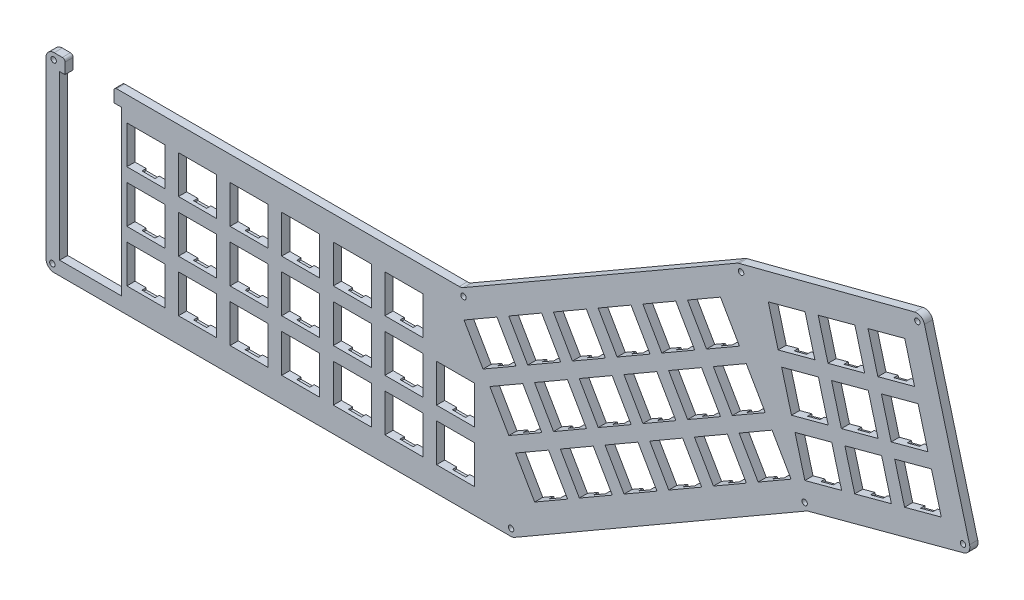
SolidWorks part; units mm, degrees
ref_plane "Plan de face" through (0, 0, 0) normal (0, 0, 1) x (1, 0, 0)
ref_plane "Plan de dessus" through (0, 0, 0) normal (0, 1, 0) x (1, 0, 0)
ref_plane "Plan de droite" through (0, 0, 0) normal (1, 0, 0) x (0, 0, -1)
sketch "Model" plane through (0, 0, 0) normal (0, 0, 1) x (1, 0, 0)
  line L0 (-149.6088, -15.6876) -> (-135.6088, -15.6876) construction
  line L1 (-149.6088, 3.3124) -> (-135.6088, 3.3124) construction
  line L2 (-149.6088, 3.3124) -> (-149.6088, -10.6876) construction
  line L3 (-149.6088, -10.6876) -> (-135.6088, -10.6876) construction
  line L4 (-135.6088, 3.3124) -> (-135.6088, -10.6876) construction
  line L5 (-149.6088, -15.6876) -> (-149.6088, -29.6876) construction
  line L6 (-149.6088, -29.6876) -> (-135.6088, -29.6876) construction
  line L7 (-135.6088, -15.6876) -> (-135.6088, -29.6876) construction
  line L8 (-149.6088, -34.6876) -> (-135.6088, -34.6876) construction
  line L9 (-149.6088, -34.6876) -> (-149.6088, -48.6876) construction
  line L10 (-149.6088, -48.6876) -> (-135.6088, -48.6876) construction
  line L11 (-135.6088, -34.6876) -> (-135.6088, -48.6876) construction
  line L12 (-149.6088, 3.3124) -> (-149.6088, -15.6876) construction
  line L13 (-130.6088, -15.6876) -> (-116.6088, -15.6876) construction
  line L14 (-130.6088, 3.3124) -> (-116.6088, 3.3124) construction
  line L15 (-130.6088, 3.3124) -> (-130.6088, -10.6876) construction
  line L16 (-130.6088, -10.6876) -> (-116.6088, -10.6876) construction
  line L17 (-116.6088, 3.3124) -> (-116.6088, -10.6876) construction
  line L18 (-130.6088, -15.6876) -> (-130.6088, -29.6876) construction
  line L19 (-130.6088, -29.6876) -> (-116.6088, -29.6876) construction
  line L20 (-116.6088, -15.6876) -> (-116.6088, -29.6876) construction
  line L21 (-130.6088, -34.6876) -> (-116.6088, -34.6876) construction
  line L22 (-130.6088, -34.6876) -> (-130.6088, -48.6876) construction
  line L23 (-130.6088, -48.6876) -> (-116.6088, -48.6876) construction
  line L24 (-116.6088, -34.6876) -> (-116.6088, -48.6876) construction
  line L25 (-130.6088, 3.3124) -> (-130.6088, -15.6876) construction
  line L26 (-111.6088, -15.6876) -> (-97.6088, -15.6876) construction
  line L27 (-111.6088, 3.3124) -> (-97.6088, 3.3124) construction
  line L28 (-111.6088, 3.3124) -> (-111.6088, -10.6876) construction
  line L29 (-111.6088, -10.6876) -> (-97.6088, -10.6876) construction
  line L30 (-97.6088, 3.3124) -> (-97.6088, -10.6876) construction
  line L31 (-111.6088, -15.6876) -> (-111.6088, -29.6876) construction
  line L32 (-111.6088, -29.6876) -> (-97.6088, -29.6876) construction
  line L33 (-97.6088, -15.6876) -> (-97.6088, -29.6876) construction
  line L34 (-111.6088, -34.6876) -> (-97.6088, -34.6876) construction
  line L35 (-111.6088, -34.6876) -> (-111.6088, -48.6876) construction
  line L36 (-111.6088, -48.6876) -> (-97.6088, -48.6876) construction
  line L37 (-97.6088, -34.6876) -> (-97.6088, -48.6876) construction
  line L38 (-111.6088, 3.3124) -> (-111.6088, -15.6876) construction
  line L39 (-92.6088, -15.6876) -> (-78.6088, -15.6876) construction
  line L40 (-92.6088, 3.3124) -> (-78.6088, 3.3124) construction
  line L41 (-92.6088, 3.3124) -> (-92.6088, -10.6876) construction
  line L42 (-92.6088, -10.6876) -> (-78.6088, -10.6876) construction
  line L43 (-78.6088, 3.3124) -> (-78.6088, -10.6876) construction
  line L44 (-92.6088, -15.6876) -> (-92.6088, -29.6876) construction
  line L45 (-92.6088, -29.6876) -> (-78.6088, -29.6876) construction
  line L46 (-78.6088, -15.6876) -> (-78.6088, -29.6876) construction
  line L47 (-92.6088, -34.6876) -> (-78.6088, -34.6876) construction
  line L48 (-92.6088, -34.6876) -> (-92.6088, -48.6876) construction
  line L49 (-92.6088, -48.6876) -> (-78.6088, -48.6876) construction
  line L50 (-78.6088, -34.6876) -> (-78.6088, -48.6876) construction
  line L51 (-92.6088, 3.3124) -> (-92.6088, -15.6876) construction
  line L52 (-73.6088, -15.6876) -> (-59.6088, -15.6876) construction
  line L53 (-73.6088, 3.3124) -> (-59.6088, 3.3124) construction
  line L54 (-73.6088, 3.3124) -> (-73.6088, -10.6876) construction
  line L55 (-73.6088, -10.6876) -> (-59.6088, -10.6876) construction
  line L56 (-59.6088, 3.3124) -> (-59.6088, -10.6876) construction
  line L57 (-73.6088, -15.6876) -> (-73.6088, -29.6876) construction
  line L58 (-73.6088, -29.6876) -> (-59.6088, -29.6876) construction
  line L59 (-59.6088, -15.6876) -> (-59.6088, -29.6876) construction
  line L60 (-73.6088, -34.6876) -> (-59.6088, -34.6876) construction
  line L61 (-73.6088, -34.6876) -> (-73.6088, -48.6876) construction
  line L62 (-73.6088, -48.6876) -> (-59.6088, -48.6876) construction
  line L63 (-59.6088, -34.6876) -> (-59.6088, -48.6876) construction
  line L64 (-73.6088, 3.3124) -> (-73.6088, -15.6876) construction
  line L65 (-54.6088, -15.6876) -> (-40.6088, -15.6876) construction
  line L66 (-54.6088, 3.3124) -> (-40.6088, 3.3124) construction
  line L67 (-54.6088, 3.3124) -> (-54.6088, -10.6876) construction
  line L68 (-54.6088, -10.6876) -> (-40.6088, -10.6876) construction
  line L69 (-40.6088, 3.3124) -> (-40.6088, -10.6876) construction
  line L70 (-54.6088, -15.6876) -> (-54.6088, -29.6876) construction
  line L71 (-54.6088, -29.6876) -> (-40.6088, -29.6876) construction
  line L72 (-40.6088, -15.6876) -> (-40.6088, -29.6876) construction
  line L73 (-54.6088, -34.6876) -> (-40.6088, -34.6876) construction
  line L74 (-54.6088, -34.6876) -> (-54.6088, -48.6876) construction
  line L75 (-54.6088, -48.6876) -> (-40.6088, -48.6876) construction
  line L76 (-40.6088, -34.6876) -> (-40.6088, -48.6876) construction
  line L77 (-54.6088, 3.3124) -> (-54.6088, -15.6876) construction
  line L78 (-35.6088, -15.6876) -> (-21.6088, -15.6876) construction
  line L79 (-35.6088, 3.3124) -> (-21.6088, 3.3124) construction
  line L80 (-35.6088, 3.3124) -> (-35.6088, -10.6876) construction
  line L81 (-35.6088, -10.6876) -> (-21.6088, -10.6876) construction
  line L82 (-21.6088, 3.3124) -> (-21.6088, -10.6876) construction
  line L83 (-35.6088, -15.6876) -> (-35.6088, -29.6876) construction
  line L84 (-35.6088, -29.6876) -> (-21.6088, -29.6876) construction
  line L85 (-21.6088, -15.6876) -> (-21.6088, -29.6876) construction
  line L86 (-35.6088, -34.6876) -> (-21.6088, -34.6876) construction
  line L87 (-35.6088, -34.6876) -> (-35.6088, -48.6876) construction
  line L88 (-35.6088, -48.6876) -> (-21.6088, -48.6876) construction
  line L89 (-21.6088, -34.6876) -> (-21.6088, -48.6876) construction
  line L90 (-35.6088, 3.3124) -> (-35.6088, -15.6876) construction
  line L91 (-149.6088, -15.6876) -> (-130.6088, -15.6876) construction
  line L92 (-19.6088, -13.6876) -> (-18.8669, -14.9725) construction
  line L93 (-37.6088, 5.3124) -> (-19.6088, 5.3124) construction
  line L94 (-19.6088, 5.3124) -> (-19.6088, -12.6876) construction
  line L95 (-37.6088, -12.6876) -> (-19.6088, -12.6876) construction
  line L96 (-37.6088, 5.3124) -> (-37.6088, -12.6876) construction
  line L97 (-56.6088, 5.3124) -> (-38.6088, 5.3124) construction
  line L98 (-38.6088, 5.3124) -> (-38.6088, -12.6876) construction
  line L99 (-56.6088, -12.6876) -> (-38.6088, -12.6876) construction
  line L100 (-56.6088, 5.3124) -> (-56.6088, -12.6876) construction
  line L101 (3.8161, 21.7392) -> (12.8161, 6.1508) construction
  line L102 (12.8161, 6.1508) -> (-2.7723, -2.8492) construction
  line L103 (-11.7723, 12.7392) -> (-2.7723, -2.8492) construction
  line L104 (3.8161, 21.7392) -> (-11.7723, 12.7392) construction
  line L105 (-12.6383, 12.2392) -> (-3.6383, -3.3492) construction
  line L106 (-3.6383, -3.3492) -> (-19.2268, -12.3492) construction
  line L107 (-28.2268, 3.2392) -> (-19.2268, -12.3492) construction
  line L108 (-12.6383, 12.2392) -> (-28.2268, 3.2392) construction
  line L109 (88.6341, 26.8303) -> (73.0456, 17.8303) construction
  line L110 (-13.3704, 9.5072) -> (-3.8704, -6.9473) construction
  line L111 (3.0841, 19.0072) -> (12.5841, 2.5527) construction
  line L112 (19.5386, 28.5072) -> (29.0386, 12.0527) construction
  line L113 (35.9931, 38.0072) -> (45.4931, 21.5527) construction
  line L114 (52.4475, 47.5072) -> (61.9475, 31.0527) construction
  line L115 (68.902, 57.0072) -> (78.402, 40.5527) construction
  line L116 (73.0456, 17.8303) -> (82.0456, 2.2418) construction
  line L117 (-6.4947, -30.4018) -> (0.5053, -42.5261) construction
  line L118 (12.6296, -35.5261) -> (0.5053, -42.5261) construction
  line L119 (5.6296, -23.4018) -> (12.6296, -35.5261) construction
  line L120 (5.6296, -23.4018) -> (-6.4947, -30.4018) construction
  line L121 (-15.9947, -13.9473) -> (-8.9947, -26.0717) construction
  line L122 (3.1296, -19.0717) -> (-8.9947, -26.0717) construction
  line L123 (-3.8704, -6.9473) -> (3.1296, -19.0717) construction
  line L124 (-25.4947, 2.5072) -> (-18.4947, -9.6172) construction
  line L125 (-6.3704, -2.6172) -> (-18.4947, -9.6172) construction
  line L126 (-13.3704, 9.5072) -> (-6.3704, -2.6172) construction
  line L127 (-13.3704, 9.5072) -> (-25.4947, 2.5072) construction
  line L128 (-3.8704, -6.9473) -> (-15.9947, -13.9473) construction
  line L129 (9.9597, -20.9018) -> (16.9597, -33.0261) construction
  line L130 (29.0841, -26.0261) -> (16.9597, -33.0261) construction
  line L131 (22.0841, -13.9018) -> (29.0841, -26.0261) construction
  line L132 (22.0841, -13.9018) -> (9.9597, -20.9018) construction
  line L133 (0.4597, -4.4473) -> (7.4597, -16.5717) construction
  line L134 (19.5841, -9.5717) -> (7.4597, -16.5717) construction
  line L135 (12.5841, 2.5527) -> (19.5841, -9.5717) construction
  line L136 (-9.0403, 12.0072) -> (-2.0403, -0.1172) construction
  line L137 (10.0841, 6.8828) -> (-2.0403, -0.1172) construction
  line L138 (3.0841, 19.0072) -> (10.0841, 6.8828) construction
  line L139 (3.0841, 19.0072) -> (-9.0403, 12.0072) construction
  line L140 (12.5841, 2.5527) -> (0.4597, -4.4473) construction
  line L141 (26.4142, -11.4018) -> (33.4142, -23.5261) construction
  line L142 (45.5386, -16.5261) -> (33.4142, -23.5261) construction
  line L143 (38.5386, -4.4018) -> (45.5386, -16.5261) construction
  line L144 (38.5386, -4.4018) -> (26.4142, -11.4018) construction
  line L145 (16.9142, 5.0527) -> (23.9142, -7.0717) construction
  line L146 (36.0386, -0.0717) -> (23.9142, -7.0717) construction
  line L147 (29.0386, 12.0527) -> (36.0386, -0.0717) construction
  line L148 (7.4142, 21.5072) -> (14.4142, 9.3828) construction
  line L149 (26.5386, 16.3828) -> (14.4142, 9.3828) construction
  line L150 (19.5386, 28.5072) -> (26.5386, 16.3828) construction
  line L151 (19.5386, 28.5072) -> (7.4142, 21.5072) construction
  line L152 (29.0386, 12.0527) -> (16.9142, 5.0527) construction
  line L153 (42.8687, -1.9018) -> (49.8687, -14.0261) construction
  line L154 (61.9931, -7.0261) -> (49.8687, -14.0261) construction
  line L155 (54.9931, 5.0982) -> (61.9931, -7.0261) construction
  line L156 (54.9931, 5.0982) -> (42.8687, -1.9018) construction
  line L157 (33.3687, 14.5527) -> (40.3687, 2.4283) construction
  line L158 (52.4931, 9.4283) -> (40.3687, 2.4283) construction
  line L159 (45.4931, 21.5527) -> (52.4931, 9.4283) construction
  line L160 (23.8687, 31.0072) -> (30.8687, 18.8828) construction
  line L161 (42.9931, 25.8828) -> (30.8687, 18.8828) construction
  line L162 (35.9931, 38.0072) -> (42.9931, 25.8828) construction
  line L163 (35.9931, 38.0072) -> (23.8687, 31.0072) construction
  line L164 (45.4931, 21.5527) -> (33.3687, 14.5527) construction
  line L165 (59.3232, 7.5982) -> (66.3232, -4.5261) construction
  line L166 (78.4475, 2.4739) -> (66.3232, -4.5261) construction
  line L167 (71.4475, 14.5982) -> (78.4475, 2.4739) construction
  line L168 (71.4475, 14.5982) -> (59.3232, 7.5982) construction
  line L169 (49.8232, 24.0527) -> (56.8232, 11.9283) construction
  line L170 (68.9475, 18.9283) -> (56.8232, 11.9283) construction
  line L171 (61.9475, 31.0527) -> (68.9475, 18.9283) construction
  line L172 (40.3232, 40.5072) -> (47.3232, 28.3828) construction
  line L173 (59.4475, 35.3828) -> (47.3232, 28.3828) construction
  line L174 (52.4475, 47.5072) -> (59.4475, 35.3828) construction
  line L175 (52.4475, 47.5072) -> (40.3232, 40.5072) construction
  line L176 (61.9475, 31.0527) -> (49.8232, 24.0527) construction
  line L177 (75.7777, 17.0982) -> (82.7777, 4.9739) construction
  line L178 (94.902, 11.9739) -> (82.7777, 4.9739) construction
  line L179 (87.902, 24.0982) -> (94.902, 11.9739) construction
  line L180 (87.902, 24.0982) -> (75.7777, 17.0982) construction
  line L181 (66.2777, 33.5527) -> (73.2777, 21.4283) construction
  line L182 (85.402, 28.4283) -> (73.2777, 21.4283) construction
  line L183 (78.402, 40.5527) -> (85.402, 28.4283) construction
  line L184 (56.7777, 50.0072) -> (63.7777, 37.8828) construction
  line L185 (75.902, 44.8828) -> (63.7777, 37.8828) construction
  line L186 (68.902, 57.0072) -> (75.902, 44.8828) construction
  line L187 (68.902, 57.0072) -> (56.7777, 50.0072) construction
  line L188 (78.402, 40.5527) -> (66.2777, 33.5527) construction
  line L189 (97.6341, 11.2418) -> (82.0456, 2.2418) construction
  line L190 (88.6341, 26.8303) -> (97.6341, 11.2418) construction
  line L191 (102.6968, 0.3259) -> (93.4333, 22.69) construction
  line L192 (93.8992, 29.0112) -> (98.558, 11.6245) construction
  line L193 (98.558, 11.6245) -> (115.9446, 16.2832) construction
  line L194 (111.2859, 33.6699) -> (115.9446, 16.2832) construction
  line L195 (86.5136, 64.3021) -> (91.4311, 45.9495) construction
  line L196 (93.8992, 29.0112) -> (111.2859, 33.6699) construction
  line L197 (91.4311, 45.9495) -> (104.9541, 49.573) construction
  line L198 (86.5136, 64.3021) -> (100.0365, 67.9256) construction
  line L199 (86.5136, 64.3021) -> (90.137, 50.7792) construction
  line L200 (90.137, 50.7792) -> (103.66, 54.4026) construction
  line L201 (100.0365, 67.9256) -> (103.66, 54.4026) construction
  line L202 (91.4311, 45.9495) -> (95.0546, 32.4266) construction
  line L203 (95.0546, 32.4266) -> (108.5776, 36.05) construction
  line L204 (104.9541, 49.573) -> (108.5776, 36.05) construction
  line L205 (96.3487, 27.5969) -> (109.8717, 31.2204) construction
  line L206 (96.3487, 27.5969) -> (99.9722, 14.074) construction
  line L207 (99.9722, 14.074) -> (113.4951, 17.6974) construction
  line L208 (109.8717, 31.2204) -> (113.4951, 17.6974) construction
  line L209 (109.7837, 50.8671) -> (123.3067, 54.4906) construction
  line L210 (104.8662, 69.2197) -> (118.3891, 72.8432) construction
  line L211 (104.8662, 69.2197) -> (108.4896, 55.6967) construction
  line L212 (108.4896, 55.6967) -> (122.0126, 59.3202) construction
  line L213 (118.3891, 72.8432) -> (122.0126, 59.3202) construction
  line L214 (109.7837, 50.8671) -> (113.4072, 37.3441) construction
  line L215 (113.4072, 37.3441) -> (126.9302, 40.9676) construction
  line L216 (123.3067, 54.4906) -> (126.9302, 40.9676) construction
  line L217 (114.7013, 32.5145) -> (128.2243, 36.138) construction
  line L218 (114.7013, 32.5145) -> (118.3248, 18.9915) construction
  line L219 (118.3248, 18.9915) -> (131.8477, 22.615) construction
  line L220 (128.2243, 36.138) -> (131.8477, 22.615) construction
  line L221 (112.2518, 33.9287) -> (116.9105, 16.5421) construction
  line L222 (116.9105, 16.5421) -> (134.2972, 21.2008) construction
  line L223 (129.6385, 38.5875) -> (134.2972, 21.2008) construction
  line L224 (104.8662, 69.2197) -> (109.7837, 50.8671) construction
  line L225 (112.2518, 33.9287) -> (129.6385, 38.5875) construction
  line L226 (128.1363, 55.7847) -> (141.6593, 59.4081) construction
  line L227 (123.2188, 74.1372) -> (136.7417, 77.7607) construction
  line L228 (123.2188, 74.1372) -> (126.8422, 60.6143) construction
  line L229 (126.8422, 60.6143) -> (140.3652, 64.2378) construction
  line L230 (136.7417, 77.7607) -> (140.3652, 64.2378) construction
  line L231 (128.1363, 55.7847) -> (131.7598, 42.2617) construction
  line L232 (131.7598, 42.2617) -> (145.2828, 45.8852) construction
  line L233 (141.6593, 59.4081) -> (145.2828, 45.8852) construction
  line L234 (133.0539, 37.4321) -> (146.5768, 41.0555) construction
  line L235 (133.0539, 37.4321) -> (136.6774, 23.9091) construction
  line L236 (136.6774, 23.9091) -> (150.2003, 27.5326) construction
  line L237 (146.5768, 41.0555) -> (150.2003, 27.5326) construction
  line L238 (130.6044, 38.8463) -> (135.2631, 21.4596) construction
  line L239 (135.2631, 21.4596) -> (152.6498, 26.1184) construction
  line L240 (147.9911, 43.505) -> (152.6498, 26.1184) construction
  line L241 (123.2188, 74.1372) -> (128.1363, 55.7847) construction
  line L242 (130.6044, 38.8463) -> (147.9911, 43.505) construction
  line L243 (91.4311, 45.9495) -> (109.7837, 50.8671) construction
  line L244 (-37.6088, -13.6876) -> (-19.6088, -13.6876) construction
  line L245 (-19.6088, -13.6876) -> (-19.6088, -31.6876) construction
  line L246 (-37.6088, -31.6876) -> (-19.6088, -31.6876) construction
  line L247 (-37.6088, -13.6876) -> (-37.6088, -31.6876) construction
  line L248 (-3.1383, -4.2153) -> (-18.7268, -13.2153) construction
  line L249 (-18.7268, -13.2153) -> (-9.7268, -28.8037) construction
  line L250 (5.8617, -19.8037) -> (-9.7268, -28.8037) construction
  line L251 (-3.1383, -4.2153) -> (5.8617, -19.8037) construction
  line L252 (-18.7268, -13.2153) -> (-18.009, -14.4585) construction
  line L253 (88.9817, 47.3637) -> (93.6404, 29.9771) construction
  line L254 (93.6404, 29.9771) -> (111.0271, 34.6358) construction
  line L255 (106.3683, 52.0225) -> (111.0271, 34.6358) construction
  line L256 (88.9817, 47.3637) -> (106.3683, 52.0225) construction
  line L257 (79.1341, 43.2847) -> (88.1341, 27.6963) construction
  line L258 (88.1341, 27.6963) -> (72.5456, 18.6963) construction
  line L259 (63.5456, 34.2847) -> (72.5456, 18.6963) construction
  line L260 (79.1341, 43.2847) -> (63.5456, 34.2847) construction
  line L261 (120.7693, 75.5515) -> (138.1559, 80.2102) construction
  line L262 (-170.3739, 2.0225) -> (-152.3739, 2.0225) construction
  line L263 (-170.3739, 2.0225) -> (-170.3739, -30.9775) construction
  line L264 (-170.3739, -30.9775) -> (-152.3739, -30.9775) construction
  line L265 (-152.3739, 2.0225) -> (-152.3739, -30.9775) construction
  line L266 (138.1559, 80.2102) -> (142.8147, 62.8235) construction
  line L267 (125.428, 58.1648) -> (142.8147, 62.8235) construction
  line L268 (120.7693, 75.5515) -> (125.428, 58.1648) construction
  line L269 (-151.6088, -50.6876) -> (-133.6088, -50.6876) construction
  line L270 (-133.6088, -32.6876) -> (-133.6088, -50.6876) construction
  line L271 (-151.6088, -32.6876) -> (-133.6088, -32.6876) construction
  line L272 (-151.6088, -32.6876) -> (-151.6088, -50.6876) construction
  line L273 (-37.6088, -50.6876) -> (-19.6088, -50.6876) construction
  line L274 (-19.6088, -32.6876) -> (-19.6088, -50.6876) construction
  line L275 (-37.6088, -32.6876) -> (-19.6088, -32.6876) construction
  line L276 (-37.6088, -32.6876) -> (-37.6088, -50.6876) construction
  line L277 (-151.6088, 5.3124) -> (-133.6088, 5.3124) construction
  line L278 (-133.6088, 5.3124) -> (-133.6088, -12.6876) construction
  line L279 (-151.6088, -12.6876) -> (-133.6088, -12.6876) construction
  line L280 (-151.6088, 5.3124) -> (-151.6088, -12.6876) construction
  line L281 (69.6341, 59.7392) -> (54.0456, 50.7392) construction
  line L282 (54.0456, 50.7392) -> (63.0456, 35.1508) construction
  line L283 (78.6341, 44.1508) -> (63.0456, 35.1508) construction
  line L284 (69.6341, 59.7392) -> (78.6341, 44.1508) construction
  line L285 (-172.3739, 5.3124) -> (-24.636, 5.3124)
  line L286 (-24.636, 5.3124) -> (77.9848, 64.5605)
  line L287 (138.1559, 80.2102) -> (77.9848, 64.5605)
  line L288 (138.1559, 80.2102) -> (152.6498, 26.1184)
  line L289 (152.6498, 26.1184) -> (98.065, 11.5079)
  line L290 (98.065, 11.5079) -> (82.0456, 2.2418)
  line L291 (82.0456, 2.2418) -> (-9.4597, -50.6876)
  line L292 (-37.6088, -50.6876) -> (-19.6088, -50.6876)
  line L293 (-19.6088, -50.6876) -> (-9.4597, -50.6876)
  line L294 (-172.3739, 5.3124) -> (-172.3739, -50.6876)
  line L295 (-172.3739, -50.6876) -> (-37.6088, -50.6876)
  line L296 (101.9307, 2.1754) -> (100.0173, 6.7948) construction
  line L297 (-152.3739, 2.0225) -> (-172.3739, 2.0225) construction
  line L298 (-152.3739, 5.3124) -> (-172.3739, 5.3124) construction
  line L299 (-152.3739, 5.3124) -> (-152.3739, -32.6876) construction
  line L300 (-152.3739, -32.6876) -> (-172.3739, -32.6876) construction
  line L301 (-172.3739, 5.3124) -> (-172.3739, -32.6876) construction
  circle A0 centre (100.0173, 6.7948) radius 1.5 construction
sketch "Esquisse9" plane through (0, 0, 0) normal (0, 0, 1) x (1, 0, 0)
  line L0 (152.8114, 25.9717) -> (138.2826, 80.2215) construction
  line L1 (98.1506, 11.3316) -> (152.8114, 25.9717) construction
  line L2 (-9.3986, -50.8585) -> (98.1506, 11.3316) construction
  line L3 (-172.3739, -50.8585) -> (-9.3986, -50.8585) construction
  line L4 (-24.5886, 5.3017) -> (-172.3739, 5.2915) construction
  line L5 (138.2826, 80.2215) -> (78.0109, 64.5416) construction
  line L6 (-151.6088, 5.3124) -> (-151.6088, 5.2929)
  line L7 (-24.5886, 5.3017) -> (78.0109, 64.5416) construction
  line L8 (-172.3739, 5.2915) -> (-172.3739, -50.6876) construction
  line L9 (-172.3739, -50.6876) -> (-172.3739, -50.8585) construction
  line L10 (-25.1245, 7.3016) -> (-174.3739, 7.2914)
  line L11 (-174.3739, 7.2914) -> (-174.3739, -50.6876)
  line L12 (-174.3739, -50.6876) -> (-174.3739, -52.8585)
  line L13 (-174.3739, -52.8585) -> (-8.862, -52.8585)
  line L14 (-8.862, -52.8585) -> (98.9231, 9.4681)
  line L15 (98.9231, 9.4681) -> (155.2607, 24.5572)
  line L16 (155.2607, 24.5572) -> (139.7008, 82.657)
  line L17 (139.7008, 82.657) -> (77.2454, 66.409)
  line L18 (-25.1245, 7.3016) -> (77.2454, 66.409)
  line L19 (-26.4645, 12.3015) -> (-179.3739, 12.291)
  line L20 (-179.3739, 12.291) -> (-179.3739, -50.6876)
  line L21 (-179.3739, -50.6876) -> (-179.3739, -57.8585)
  line L22 (-179.3739, -57.8585) -> (-7.5204, -57.8585)
  line L23 (-7.5204, -57.8585) -> (100.8545, 4.8091)
  line L24 (100.8545, 4.8091) -> (161.3839, 21.021)
  line L25 (161.3839, 21.021) -> (143.2464, 88.7459)
  line L26 (143.2464, 88.7459) -> (75.3314, 71.0775)
  line L27 (-26.4645, 12.3015) -> (75.3314, 71.0775)
  circle A0 centre (80.6856, 58.4893) radius 1
  circle A1 centre (92.8776, 28.0855) radius 1
  circle A2 centre (-29.7028, -2.6485) radius 1
  circle A3 centre (-10.6528, -46.4381) radius 1
  circle A4 centre (-114.2594, -13.4181) radius 1
  circle A5 centre (-114.0308, -32.4935) radius 1
  dimension "D1" = 2
  dimension "D2" = 5
sketch "Esquisse2" plane through (0, 0, 0) normal (0, 0, 1) x (1, 0, 0)
  line L40 (-151.6088, 5.3124) -> (-151.6088, -50.8585)
  line L41 (-54.6088, -34.6876) -> (-54.6088, -48.6876) construction
  line L42 (-54.6088, -48.6876) -> (-40.6088, -48.6876) construction
  line L43 (-40.6088, -34.6876) -> (-40.6088, -48.6876) construction
  line L44 (-54.6088, -34.6876) -> (-40.6088, -34.6876) construction
  line L45 (-35.6088, -34.6876) -> (-35.6088, -48.6876) construction
  line L46 (-35.6088, -48.6876) -> (-21.6088, -48.6876) construction
  line L47 (-21.6088, -34.6876) -> (-21.6088, -48.6876) construction
  line L48 (-35.6088, -34.6876) -> (-21.6088, -34.6876) construction
  line L49 (-35.6088, -15.6876) -> (-35.6088, -29.6876) construction
  line L50 (-35.6088, -29.6876) -> (-21.6088, -29.6876) construction
  line L51 (-21.6088, -15.6876) -> (-21.6088, -29.6876) construction
  line L52 (-35.6088, -15.6876) -> (-21.6088, -15.6876) construction
  line L53 (-54.6088, -15.6876) -> (-54.6088, -29.6876) construction
  line L54 (-54.6088, -29.6876) -> (-40.6088, -29.6876) construction
  line L55 (-40.6088, -15.6876) -> (-40.6088, -29.6876) construction
  line L56 (-54.6088, -15.6876) -> (-40.6088, -15.6876) construction
  line L57 (-54.6088, 3.3124) -> (-54.6088, -10.6876) construction
  line L58 (-54.6088, -10.6876) -> (-40.6088, -10.6876) construction
  line L59 (-40.6088, 3.3124) -> (-40.6088, -10.6876) construction
  line L60 (-54.6088, 3.3124) -> (-40.6088, 3.3124) construction
  line L61 (-73.6088, -34.6876) -> (-73.6088, -48.6876) construction
  line L62 (-73.6088, -48.6876) -> (-59.6088, -48.6876) construction
  line L63 (-59.6088, -34.6876) -> (-59.6088, -48.6876) construction
  line L64 (-73.6088, -34.6876) -> (-59.6088, -34.6876) construction
  line L65 (-73.6088, -15.6876) -> (-73.6088, -29.6876) construction
  line L66 (-73.6088, -29.6876) -> (-59.6088, -29.6876) construction
  line L67 (-59.6088, -15.6876) -> (-59.6088, -29.6876) construction
  line L68 (-73.6088, -15.6876) -> (-59.6088, -15.6876) construction
  line L69 (-73.6088, 3.3124) -> (-73.6088, -10.6876) construction
  line L70 (-73.6088, -10.6876) -> (-59.6088, -10.6876) construction
  line L71 (-59.6088, 3.3124) -> (-59.6088, -10.6876) construction
  line L72 (-73.6088, 3.3124) -> (-59.6088, 3.3124) construction
  line L73 (-92.6088, -34.6876) -> (-92.6088, -48.6876) construction
  line L74 (-92.6088, -48.6876) -> (-78.6088, -48.6876) construction
  line L75 (-78.6088, -34.6876) -> (-78.6088, -48.6876) construction
  line L76 (-92.6088, -34.6876) -> (-78.6088, -34.6876) construction
  line L77 (-92.6088, -15.6876) -> (-92.6088, -29.6876) construction
  line L78 (-92.6088, -29.6876) -> (-78.6088, -29.6876) construction
  line L79 (-78.6088, -15.6876) -> (-78.6088, -29.6876) construction
  line L80 (-92.6088, -15.6876) -> (-78.6088, -15.6876) construction
  line L81 (-92.6088, 3.3124) -> (-92.6088, -10.6876) construction
  line L82 (-92.6088, -10.6876) -> (-78.6088, -10.6876) construction
  line L83 (-78.6088, 3.3124) -> (-78.6088, -10.6876) construction
  line L84 (-92.6088, 3.3124) -> (-78.6088, 3.3124) construction
  line L85 (-111.6088, -34.6876) -> (-111.6088, -48.6876) construction
  line L86 (-111.6088, -48.6876) -> (-97.6088, -48.6876) construction
  line L87 (-97.6088, -34.6876) -> (-97.6088, -48.6876) construction
  line L88 (-111.6088, -34.6876) -> (-97.6088, -34.6876) construction
  line L89 (-111.6088, -15.6876) -> (-111.6088, -29.6876) construction
  line L90 (-111.6088, -29.6876) -> (-97.6088, -29.6876) construction
  line L91 (-97.6088, -15.6876) -> (-97.6088, -29.6876) construction
  line L92 (-111.6088, -15.6876) -> (-97.6088, -15.6876) construction
  line L93 (-130.6088, -34.6876) -> (-130.6088, -48.6876) construction
  line L94 (-130.6088, -48.6876) -> (-116.6088, -48.6876) construction
  line L95 (-116.6088, -34.6876) -> (-116.6088, -48.6876) construction
  line L96 (-130.6088, -34.6876) -> (-116.6088, -34.6876) construction
  line L97 (-130.6088, -15.6876) -> (-130.6088, -29.6876) construction
  line L98 (-130.6088, -29.6876) -> (-116.6088, -29.6876) construction
  line L99 (-116.6088, -15.6876) -> (-116.6088, -29.6876) construction
  line L100 (-130.6088, -15.6876) -> (-116.6088, -15.6876) construction
  line L101 (-149.6088, -34.6876) -> (-149.6088, -48.6876) construction
  line L102 (-149.6088, -48.6876) -> (-135.6088, -48.6876) construction
  line L103 (-135.6088, -34.6876) -> (-135.6088, -48.6876) construction
  line L104 (-149.6088, -34.6876) -> (-135.6088, -34.6876) construction
  line L105 (-149.6088, -15.6876) -> (-149.6088, -29.6876) construction
  line L106 (-149.6088, -29.6876) -> (-135.6088, -29.6876) construction
  line L107 (-135.6088, -15.6876) -> (-135.6088, -29.6876) construction
  line L108 (-149.6088, -15.6876) -> (-135.6088, -15.6876) construction
  line L109 (-111.6088, 3.3124) -> (-111.6088, -10.6876) construction
  line L110 (-111.6088, -10.6876) -> (-97.6088, -10.6876) construction
  line L111 (-97.6088, 3.3124) -> (-97.6088, -10.6876) construction
  line L112 (-111.6088, 3.3124) -> (-97.6088, 3.3124) construction
  line L113 (-130.6088, 3.3124) -> (-130.6088, -10.6876) construction
  line L114 (-130.6088, -10.6876) -> (-116.6088, -10.6876) construction
  line L115 (-116.6088, 3.3124) -> (-116.6088, -10.6876) construction
  line L116 (-130.6088, 3.3124) -> (-116.6088, 3.3124) construction
  line L117 (-149.6088, 3.3124) -> (-149.6088, -10.6876) construction
  line L118 (-149.6088, -10.6876) -> (-135.6088, -10.6876) construction
  line L119 (-135.6088, 3.3124) -> (-135.6088, -10.6876) construction
  line L120 (-149.6088, 3.3124) -> (-135.6088, 3.3124) construction
  line L121 (-54.6088, -34.6876) -> (-54.6088, -48.6876)
  line L122 (-54.6088, -48.6876) -> (-40.6088, -48.6876)
  line L123 (-40.6088, -34.6876) -> (-40.6088, -48.6876)
  line L124 (-54.6088, -34.6876) -> (-40.6088, -34.6876)
  line L125 (-35.6088, -34.6876) -> (-35.6088, -48.6876)
  line L126 (-35.6088, -48.6876) -> (-21.6088, -48.6876)
  line L127 (-21.6088, -34.6876) -> (-21.6088, -48.6876)
  line L128 (-35.6088, -34.6876) -> (-21.6088, -34.6876)
  line L129 (-35.6088, -15.6876) -> (-35.6088, -29.6876)
  line L130 (-35.6088, -29.6876) -> (-21.6088, -29.6876)
  line L131 (-21.6088, -15.6876) -> (-21.6088, -29.6876)
  line L132 (-35.6088, -15.6876) -> (-21.6088, -15.6876)
  line L133 (-54.6088, -15.6876) -> (-54.6088, -29.6876)
  line L134 (-54.6088, -29.6876) -> (-40.6088, -29.6876)
  line L135 (-40.6088, -15.6876) -> (-40.6088, -29.6876)
  line L136 (-54.6088, -15.6876) -> (-40.6088, -15.6876)
  line L137 (-54.6088, 3.3124) -> (-54.6088, -10.6876)
  line L138 (-54.6088, -10.6876) -> (-40.6088, -10.6876)
  line L139 (-40.6088, 3.3124) -> (-40.6088, -10.6876)
  line L140 (-54.6088, 3.3124) -> (-40.6088, 3.3124)
  line L141 (-73.6088, -34.6876) -> (-73.6088, -48.6876)
  line L142 (-73.6088, -48.6876) -> (-59.6088, -48.6876)
  line L143 (-59.6088, -34.6876) -> (-59.6088, -48.6876)
  line L144 (-73.6088, -34.6876) -> (-59.6088, -34.6876)
  line L145 (-73.6088, -15.6876) -> (-73.6088, -29.6876)
  line L146 (-73.6088, -29.6876) -> (-59.6088, -29.6876)
  line L147 (-59.6088, -15.6876) -> (-59.6088, -29.6876)
  line L148 (-73.6088, -15.6876) -> (-59.6088, -15.6876)
  line L149 (-73.6088, 3.3124) -> (-73.6088, -10.6876)
  line L150 (-73.6088, -10.6876) -> (-59.6088, -10.6876)
  line L151 (-59.6088, 3.3124) -> (-59.6088, -10.6876)
  line L152 (-73.6088, 3.3124) -> (-59.6088, 3.3124)
  line L153 (-92.6088, -34.6876) -> (-92.6088, -48.6876)
  line L154 (-92.6088, -48.6876) -> (-78.6088, -48.6876)
  line L155 (-78.6088, -34.6876) -> (-78.6088, -48.6876)
  line L156 (-92.6088, -34.6876) -> (-78.6088, -34.6876)
  line L157 (-92.6088, -15.6876) -> (-92.6088, -29.6876)
  line L158 (-92.6088, -29.6876) -> (-78.6088, -29.6876)
  line L159 (-78.6088, -15.6876) -> (-78.6088, -29.6876)
  line L160 (-92.6088, -15.6876) -> (-78.6088, -15.6876)
  line L161 (-92.6088, 3.3124) -> (-92.6088, -10.6876)
  line L162 (-92.6088, -10.6876) -> (-78.6088, -10.6876)
  line L163 (-78.6088, 3.3124) -> (-78.6088, -10.6876)
  line L164 (-92.6088, 3.3124) -> (-78.6088, 3.3124)
  line L165 (-111.6088, -34.6876) -> (-111.6088, -48.6876)
  line L166 (-111.6088, -48.6876) -> (-97.6088, -48.6876)
  line L167 (-97.6088, -34.6876) -> (-97.6088, -48.6876)
  line L168 (-111.6088, -34.6876) -> (-97.6088, -34.6876)
  line L169 (-111.6088, -15.6876) -> (-111.6088, -29.6876)
  line L170 (-111.6088, -29.6876) -> (-97.6088, -29.6876)
  line L171 (-97.6088, -15.6876) -> (-97.6088, -29.6876)
  line L172 (-111.6088, -15.6876) -> (-97.6088, -15.6876)
  line L173 (-130.6088, -34.6876) -> (-130.6088, -48.6876)
  line L174 (-130.6088, -48.6876) -> (-116.6088, -48.6876)
  line L175 (-116.6088, -34.6876) -> (-116.6088, -48.6876)
  line L176 (-130.6088, -34.6876) -> (-116.6088, -34.6876)
  line L177 (-130.6088, -15.6876) -> (-130.6088, -29.6876)
  line L178 (-130.6088, -29.6876) -> (-116.6088, -29.6876)
  line L179 (-116.6088, -15.6876) -> (-116.6088, -29.6876)
  line L180 (-130.6088, -15.6876) -> (-116.6088, -15.6876)
  line L181 (-149.6088, -34.6876) -> (-149.6088, -48.6876)
  line L182 (-149.6088, -48.6876) -> (-135.6088, -48.6876)
  line L183 (-135.6088, -34.6876) -> (-135.6088, -48.6876)
  line L184 (-149.6088, -34.6876) -> (-135.6088, -34.6876)
  line L185 (-149.6088, -15.6876) -> (-149.6088, -29.6876)
  line L186 (-149.6088, -29.6876) -> (-135.6088, -29.6876)
  line L187 (-135.6088, -15.6876) -> (-135.6088, -29.6876)
  line L188 (-149.6088, -15.6876) -> (-135.6088, -15.6876)
  line L189 (-111.6088, 3.3124) -> (-111.6088, -10.6876)
  line L190 (-111.6088, -10.6876) -> (-97.6088, -10.6876)
  line L191 (-97.6088, 3.3124) -> (-97.6088, -10.6876)
  line L192 (-111.6088, 3.3124) -> (-97.6088, 3.3124)
  line L193 (-130.6088, 3.3124) -> (-130.6088, -10.6876)
  line L194 (-130.6088, -10.6876) -> (-116.6088, -10.6876)
  line L195 (-116.6088, 3.3124) -> (-116.6088, -10.6876)
  line L196 (-130.6088, 3.3124) -> (-116.6088, 3.3124)
  line L197 (-149.6088, 3.3124) -> (-149.6088, -10.6876)
  line L198 (-149.6088, -10.6876) -> (-135.6088, -10.6876)
  line L199 (-135.6088, 3.3124) -> (-135.6088, -10.6876)
  line L200 (-149.6088, 3.3124) -> (-135.6088, 3.3124)
  line L201 (96.3487, 27.5969) -> (99.9722, 14.074) construction
  line L202 (99.9722, 14.074) -> (113.4951, 17.6974) construction
  line L203 (109.8717, 31.2204) -> (113.4951, 17.6974) construction
  line L204 (96.3487, 27.5969) -> (109.8717, 31.2204) construction
  line L205 (91.4311, 45.9495) -> (95.0546, 32.4266) construction
  line L206 (95.0546, 32.4266) -> (108.5776, 36.05) construction
  line L207 (104.9541, 49.573) -> (108.5776, 36.05) construction
  line L208 (91.4311, 45.9495) -> (104.9541, 49.573) construction
  line L209 (109.7837, 50.8671) -> (113.4072, 37.3441) construction
  line L210 (113.4072, 37.3441) -> (126.9302, 40.9676) construction
  line L211 (123.3067, 54.4906) -> (126.9302, 40.9676) construction
  line L212 (109.7837, 50.8671) -> (123.3067, 54.4906) construction
  line L213 (114.7013, 32.5145) -> (118.3248, 18.9915) construction
  line L214 (118.3248, 18.9915) -> (131.8477, 22.615) construction
  line L215 (128.2243, 36.138) -> (131.8477, 22.615) construction
  line L216 (114.7013, 32.5145) -> (128.2243, 36.138) construction
  line L217 (133.0539, 37.4321) -> (136.6774, 23.9091) construction
  line L218 (136.6774, 23.9091) -> (150.2003, 27.5326) construction
  line L219 (146.5768, 41.0555) -> (150.2003, 27.5326) construction
  line L220 (133.0539, 37.4321) -> (146.5768, 41.0555) construction
  line L221 (128.1363, 55.7847) -> (131.7598, 42.2617) construction
  line L222 (131.7598, 42.2617) -> (145.2828, 45.8852) construction
  line L223 (141.6593, 59.4081) -> (145.2828, 45.8852) construction
  line L224 (128.1363, 55.7847) -> (141.6593, 59.4081) construction
  line L225 (123.2188, 74.1372) -> (126.8422, 60.6143) construction
  line L226 (126.8422, 60.6143) -> (140.3652, 64.2378) construction
  line L227 (136.7417, 77.7607) -> (140.3652, 64.2378) construction
  line L228 (123.2188, 74.1372) -> (136.7417, 77.7607) construction
  line L229 (104.8662, 69.2197) -> (108.4896, 55.6967) construction
  line L230 (108.4896, 55.6967) -> (122.0126, 59.3202) construction
  line L231 (118.3891, 72.8432) -> (122.0126, 59.3202) construction
  line L232 (104.8662, 69.2197) -> (118.3891, 72.8432) construction
  line L233 (86.5136, 64.3021) -> (90.137, 50.7792) construction
  line L234 (90.137, 50.7792) -> (103.66, 54.4026) construction
  line L235 (100.0365, 67.9256) -> (103.66, 54.4026) construction
  line L236 (86.5136, 64.3021) -> (100.0365, 67.9256) construction
  line L237 (87.902, 24.0982) -> (94.902, 11.9739) construction
  line L238 (94.902, 11.9739) -> (82.7777, 4.9739) construction
  line L239 (75.7777, 17.0982) -> (82.7777, 4.9739) construction
  line L240 (87.902, 24.0982) -> (75.7777, 17.0982) construction
  line L241 (78.402, 40.5527) -> (85.402, 28.4283) construction
  line L242 (85.402, 28.4283) -> (73.2777, 21.4283) construction
  line L243 (66.2777, 33.5527) -> (73.2777, 21.4283) construction
  line L244 (78.402, 40.5527) -> (66.2777, 33.5527) construction
  line L245 (68.902, 57.0072) -> (75.902, 44.8828) construction
  line L246 (75.902, 44.8828) -> (63.7777, 37.8828) construction
  line L247 (56.7777, 50.0072) -> (63.7777, 37.8828) construction
  line L248 (68.902, 57.0072) -> (56.7777, 50.0072) construction
  line L249 (71.4475, 14.5982) -> (78.4475, 2.4739) construction
  line L250 (78.4475, 2.4739) -> (66.3232, -4.5261) construction
  line L251 (59.3232, 7.5982) -> (66.3232, -4.5261) construction
  line L252 (71.4475, 14.5982) -> (59.3232, 7.5982) construction
  line L253 (61.9475, 31.0527) -> (68.9475, 18.9283) construction
  line L254 (68.9475, 18.9283) -> (56.8232, 11.9283) construction
  line L255 (49.8232, 24.0527) -> (56.8232, 11.9283) construction
  line L256 (61.9475, 31.0527) -> (49.8232, 24.0527) construction
  line L257 (52.4475, 47.5072) -> (59.4475, 35.3828) construction
  line L258 (59.4475, 35.3828) -> (47.3232, 28.3828) construction
  line L259 (40.3232, 40.5072) -> (47.3232, 28.3828) construction
  line L260 (52.4475, 47.5072) -> (40.3232, 40.5072) construction
  line L261 (54.9931, 5.0982) -> (61.9931, -7.0261) construction
  line L262 (61.9931, -7.0261) -> (49.8687, -14.0261) construction
  line L263 (42.8687, -1.9018) -> (49.8687, -14.0261) construction
  line L264 (54.9931, 5.0982) -> (42.8687, -1.9018) construction
  line L265 (45.4931, 21.5527) -> (52.4931, 9.4283) construction
  line L266 (52.4931, 9.4283) -> (40.3687, 2.4283) construction
  line L267 (33.3687, 14.5527) -> (40.3687, 2.4283) construction
  line L268 (45.4931, 21.5527) -> (33.3687, 14.5527) construction
  line L269 (38.5386, -4.4018) -> (45.5386, -16.5261) construction
  line L270 (45.5386, -16.5261) -> (33.4142, -23.5261) construction
  line L271 (26.4142, -11.4018) -> (33.4142, -23.5261) construction
  line L272 (38.5386, -4.4018) -> (26.4142, -11.4018) construction
  line L273 (29.0386, 12.0527) -> (36.0386, -0.0717) construction
  line L274 (36.0386, -0.0717) -> (23.9142, -7.0717) construction
  line L275 (16.9142, 5.0527) -> (23.9142, -7.0717) construction
  line L276 (29.0386, 12.0527) -> (16.9142, 5.0527) construction
  line L277 (35.9931, 38.0072) -> (42.9931, 25.8828) construction
  line L278 (42.9931, 25.8828) -> (30.8687, 18.8828) construction
  line L279 (23.8687, 31.0072) -> (30.8687, 18.8828) construction
  line L280 (35.9931, 38.0072) -> (23.8687, 31.0072) construction
  line L281 (19.5386, 28.5072) -> (26.5386, 16.3828) construction
  line L282 (26.5386, 16.3828) -> (14.4142, 9.3828) construction
  line L283 (7.4142, 21.5072) -> (14.4142, 9.3828) construction
  line L284 (19.5386, 28.5072) -> (7.4142, 21.5072) construction
  line L285 (3.0841, 19.0072) -> (10.0841, 6.8828) construction
  line L286 (10.0841, 6.8828) -> (-2.0403, -0.1172) construction
  line L287 (-9.0403, 12.0072) -> (-2.0403, -0.1172) construction
  line L288 (3.0841, 19.0072) -> (-9.0403, 12.0072) construction
  line L289 (12.5841, 2.5527) -> (19.5841, -9.5717) construction
  line L290 (19.5841, -9.5717) -> (7.4597, -16.5717) construction
  line L291 (0.4597, -4.4473) -> (7.4597, -16.5717) construction
  line L292 (12.5841, 2.5527) -> (0.4597, -4.4473) construction
  line L293 (22.0841, -13.9018) -> (29.0841, -26.0261) construction
  line L294 (29.0841, -26.0261) -> (16.9597, -33.0261) construction
  line L295 (9.9597, -20.9018) -> (16.9597, -33.0261) construction
  line L296 (22.0841, -13.9018) -> (9.9597, -20.9018) construction
  line L297 (5.6296, -23.4018) -> (12.6296, -35.5261) construction
  line L298 (12.6296, -35.5261) -> (0.5053, -42.5261) construction
  line L299 (-6.4947, -30.4018) -> (0.5053, -42.5261) construction
  line L300 (5.6296, -23.4018) -> (-6.4947, -30.4018) construction
  line L301 (-3.8704, -6.9473) -> (3.1296, -19.0717) construction
  line L302 (3.1296, -19.0717) -> (-8.9947, -26.0717) construction
  line L303 (-15.9947, -13.9473) -> (-8.9947, -26.0717) construction
  line L304 (-3.8704, -6.9473) -> (-15.9947, -13.9473) construction
  line L305 (-13.3704, 9.5072) -> (-25.4947, 2.5072) construction
  line L306 (-25.4947, 2.5072) -> (-18.4947, -9.6172) construction
  line L307 (-6.3704, -2.6172) -> (-18.4947, -9.6172) construction
  line L308 (-13.3704, 9.5072) -> (-6.3704, -2.6172) construction
  line L309 (96.3487, 27.5969) -> (99.9722, 14.074)
  line L310 (99.9722, 14.074) -> (113.4951, 17.6974)
  line L311 (109.8717, 31.2204) -> (113.4951, 17.6974)
  line L312 (96.3487, 27.5969) -> (109.8717, 31.2204)
  line L313 (91.4311, 45.9495) -> (95.0546, 32.4266)
  line L314 (95.0546, 32.4266) -> (108.5776, 36.05)
  line L315 (104.9541, 49.573) -> (108.5776, 36.05)
  line L316 (91.4311, 45.9495) -> (104.9541, 49.573)
  line L317 (109.7837, 50.8671) -> (113.4072, 37.3441)
  line L318 (113.4072, 37.3441) -> (126.9302, 40.9676)
  line L319 (123.3067, 54.4906) -> (126.9302, 40.9676)
  line L320 (109.7837, 50.8671) -> (123.3067, 54.4906)
  line L321 (114.7013, 32.5145) -> (118.3248, 18.9915)
  line L322 (118.3248, 18.9915) -> (131.8477, 22.615)
  line L323 (128.2243, 36.138) -> (131.8477, 22.615)
  line L324 (114.7013, 32.5145) -> (128.2243, 36.138)
  line L325 (133.0539, 37.4321) -> (136.6774, 23.9091)
  line L326 (136.6774, 23.9091) -> (150.2003, 27.5326)
  line L327 (146.5768, 41.0555) -> (150.2003, 27.5326)
  line L328 (133.0539, 37.4321) -> (146.5768, 41.0555)
  line L329 (128.1363, 55.7847) -> (131.7598, 42.2617)
  line L330 (131.7598, 42.2617) -> (145.2828, 45.8852)
  line L331 (141.6593, 59.4081) -> (145.2828, 45.8852)
  line L332 (128.1363, 55.7847) -> (141.6593, 59.4081)
  line L333 (123.2188, 74.1372) -> (126.8422, 60.6143)
  line L334 (126.8422, 60.6143) -> (140.3652, 64.2378)
  line L335 (136.7417, 77.7607) -> (140.3652, 64.2378)
  line L336 (123.2188, 74.1372) -> (136.7417, 77.7607)
  line L337 (104.8662, 69.2197) -> (108.4896, 55.6967)
  line L338 (108.4896, 55.6967) -> (122.0126, 59.3202)
  line L339 (118.3891, 72.8432) -> (122.0126, 59.3202)
  line L340 (104.8662, 69.2197) -> (118.3891, 72.8432)
  line L341 (86.5136, 64.3021) -> (90.137, 50.7792)
  line L342 (90.137, 50.7792) -> (103.66, 54.4026)
  line L343 (100.0365, 67.9256) -> (103.66, 54.4026)
  line L344 (86.5136, 64.3021) -> (100.0365, 67.9256)
  line L345 (87.902, 24.0982) -> (94.902, 11.9739)
  line L346 (94.902, 11.9739) -> (82.7777, 4.9739)
  line L347 (75.7777, 17.0982) -> (82.7777, 4.9739)
  line L348 (87.902, 24.0982) -> (75.7777, 17.0982)
  line L349 (78.402, 40.5527) -> (85.402, 28.4283)
  line L350 (85.402, 28.4283) -> (73.2777, 21.4283)
  line L351 (66.2777, 33.5527) -> (73.2777, 21.4283)
  line L352 (78.402, 40.5527) -> (66.2777, 33.5527)
  line L353 (68.902, 57.0072) -> (75.902, 44.8828)
  line L354 (75.902, 44.8828) -> (63.7777, 37.8828)
  line L355 (56.7777, 50.0072) -> (63.7777, 37.8828)
  line L356 (68.902, 57.0072) -> (56.7777, 50.0072)
  line L357 (71.4475, 14.5982) -> (78.4475, 2.4739)
  line L358 (78.4475, 2.4739) -> (66.3232, -4.5261)
  line L359 (59.3232, 7.5982) -> (66.3232, -4.5261)
  line L360 (71.4475, 14.5982) -> (59.3232, 7.5982)
  line L361 (61.9475, 31.0527) -> (68.9475, 18.9283)
  line L362 (68.9475, 18.9283) -> (56.8232, 11.9283)
  line L363 (49.8232, 24.0527) -> (56.8232, 11.9283)
  line L364 (61.9475, 31.0527) -> (49.8232, 24.0527)
  line L365 (52.4475, 47.5072) -> (59.4475, 35.3828)
  line L366 (59.4475, 35.3828) -> (47.3232, 28.3828)
  line L367 (40.3232, 40.5072) -> (47.3232, 28.3828)
  line L368 (52.4475, 47.5072) -> (40.3232, 40.5072)
  line L369 (54.9931, 5.0982) -> (61.9931, -7.0261)
  line L370 (61.9931, -7.0261) -> (49.8687, -14.0261)
  line L371 (42.8687, -1.9018) -> (49.8687, -14.0261)
  line L372 (54.9931, 5.0982) -> (42.8687, -1.9018)
  line L373 (45.4931, 21.5527) -> (52.4931, 9.4283)
  line L374 (52.4931, 9.4283) -> (40.3687, 2.4283)
  line L375 (33.3687, 14.5527) -> (40.3687, 2.4283)
  line L376 (45.4931, 21.5527) -> (33.3687, 14.5527)
  line L377 (38.5386, -4.4018) -> (45.5386, -16.5261)
  line L378 (45.5386, -16.5261) -> (33.4142, -23.5261)
  line L379 (26.4142, -11.4018) -> (33.4142, -23.5261)
  line L380 (38.5386, -4.4018) -> (26.4142, -11.4018)
  line L381 (29.0386, 12.0527) -> (36.0386, -0.0717)
  line L382 (36.0386, -0.0717) -> (23.9142, -7.0717)
  line L383 (16.9142, 5.0527) -> (23.9142, -7.0717)
  line L384 (29.0386, 12.0527) -> (16.9142, 5.0527)
  line L385 (35.9931, 38.0072) -> (42.9931, 25.8828)
  line L386 (42.9931, 25.8828) -> (30.8687, 18.8828)
  line L387 (23.8687, 31.0072) -> (30.8687, 18.8828)
  line L388 (35.9931, 38.0072) -> (23.8687, 31.0072)
  line L389 (19.5386, 28.5072) -> (26.5386, 16.3828)
  line L390 (26.5386, 16.3828) -> (14.4142, 9.3828)
  line L391 (7.4142, 21.5072) -> (14.4142, 9.3828)
  line L392 (19.5386, 28.5072) -> (7.4142, 21.5072)
  line L393 (3.0841, 19.0072) -> (10.0841, 6.8828)
  line L394 (10.0841, 6.8828) -> (-2.0403, -0.1172)
  line L395 (-9.0403, 12.0072) -> (-2.0403, -0.1172)
  line L396 (3.0841, 19.0072) -> (-9.0403, 12.0072)
  line L397 (12.5841, 2.5527) -> (19.5841, -9.5717)
  line L398 (19.5841, -9.5717) -> (7.4597, -16.5717)
  line L399 (0.4597, -4.4473) -> (7.4597, -16.5717)
  line L400 (12.5841, 2.5527) -> (0.4597, -4.4473)
  line L401 (22.0841, -13.9018) -> (29.0841, -26.0261)
  line L402 (29.0841, -26.0261) -> (16.9597, -33.0261)
  line L403 (9.9597, -20.9018) -> (16.9597, -33.0261)
  line L404 (22.0841, -13.9018) -> (9.9597, -20.9018)
  line L405 (5.6296, -23.4018) -> (12.6296, -35.5261)
  line L406 (12.6296, -35.5261) -> (0.5053, -42.5261)
  line L407 (-6.4947, -30.4018) -> (0.5053, -42.5261)
  line L408 (5.6296, -23.4018) -> (-6.4947, -30.4018)
  line L409 (-3.8704, -6.9473) -> (3.1296, -19.0717)
  line L410 (3.1296, -19.0717) -> (-8.9947, -26.0717)
  line L411 (-15.9947, -13.9473) -> (-8.9947, -26.0717)
  line L412 (-3.8704, -6.9473) -> (-15.9947, -13.9473)
  line L413 (-13.3704, 9.5072) -> (-25.4947, 2.5072)
  line L414 (-25.4947, 2.5072) -> (-18.4947, -9.6172)
  line L415 (-6.3704, -2.6172) -> (-18.4947, -9.6172)
  line L416 (-13.3704, 9.5072) -> (-6.3704, -2.6172)
  line L417 (-26.4645, 12.3015) -> (75.3314, 71.0775) construction
  line L418 (143.2464, 88.7459) -> (75.3314, 71.0775) construction
  line L419 (161.3839, 21.021) -> (143.2464, 88.7459) construction
  line L420 (100.8545, 4.8091) -> (161.3839, 21.021) construction
  line L421 (-7.5204, -57.8585) -> (100.8545, 4.8091) construction
  line L422 (-179.3739, -57.8585) -> (-7.5204, -57.8585) construction
  line L423 (-179.3739, -50.6876) -> (-179.3739, -57.8585) construction
  line L424 (-179.3739, 12.291) -> (-179.3739, -50.6876) construction
  line L425 (-26.4645, 12.3015) -> (-179.3739, 12.291) construction
  line L426 (-26.4645, 12.3015) -> (75.3314, 71.0775)
  line L427 (143.2464, 88.7459) -> (75.3314, 71.0775)
  line L428 (161.3839, 21.021) -> (143.2464, 88.7459)
  line L429 (100.8545, 4.8091) -> (161.3839, 21.021)
  line L430 (-7.5204, -57.8585) -> (100.8545, 4.8091)
  line L431 (-179.3739, -57.8585) -> (-7.5204, -57.8585)
  line L432 (-179.3739, -50.6876) -> (-179.3739, -57.8585)
  line L433 (-179.3739, 12.291) -> (-179.3739, -50.6876)
  line L434 (-26.4645, 12.3015) -> (-179.3739, 12.291)
  line L435 (-151.6088, 5.3124) -> (-151.6088, 7.2929)
  line L436 (-25.1245, 7.3016) -> (-174.3739, 7.2914) construction
  line L437 (-151.6088, 7.2929) -> (-174.3739, 7.2914)
  line L438 (-174.3739, 7.2914) -> (-174.3739, -52.8585)
  line L439 (-174.3739, -52.8585) -> (-151.6088, -52.8585)
  line L440 (-174.3739, -52.8585) -> (-8.862, -52.8585) construction
  line L441 (-151.6088, -52.8585) -> (-151.6088, -50.8585)
extrude "Boss.-Extru.1" add sketch "Esquisse2" along normal blind 3 contours L40 L412 L409 L410 L411 L408 L405 L406 L407 L404 L401 L402 L403 L400 L397 L398 L399 L396 L393 L394 L395 L392 L389 L390 L391 region at (26.2883, 38.477, 0)
sketch "Esquisse3" plane through (0, 0, 0) normal (0, 0, -1) x (-1, 0, 0)
  line L0 (140.666, 3.3124) -> (145.496, 3.3124)
  line L1 (149.6088, 3.3124) -> (135.6088, 3.3124) construction
  line L2 (140.666, 3.3124) -> (140.666, 4.0124)
  line L3 (140.666, 4.0124) -> (145.496, 4.0124)
  line L4 (145.496, 4.0124) -> (145.496, 3.3124)
  line L5 (149.6088, -10.6876) -> (135.6088, -10.6876) construction
  line L6 (140.666, -10.6876) -> (145.496, -10.6876)
  line L7 (140.666, -10.6876) -> (140.666, -11.3876)
  line L8 (140.666, -11.3876) -> (145.496, -11.3876)
  line L9 (145.496, -10.6876) -> (145.496, -11.3876)
  point P5 (143.081, 3.3124)
  dimension "D1" = 4.83
  dimension "D2" = 0.7
  dimension "D3" = 0.7
extrude "Enlèv. mat.-Extru.1" cut sketch "Esquisse3" against normal blind 1.57
pattern_linear "Répétition linéaire1" count 3 spacing 19 along (0, -1, 0) of "Enlèv. mat.-Extru.1"
pattern_linear "Répétition linéaire2" count 6 spacing 19 along (1, 0, 0) of "Répétition linéaire1", "Enlèv. mat.-Extru.1"
sketch "Esquisse4" plane through (0, 0, 0) normal (0, 0, -1) x (-1, 0, 0)
  line L0 (26.3461, -15.6876) -> (31.1761, -15.6876)
  line L1 (35.6088, -15.6876) -> (21.6088, -15.6876) construction
  line L2 (26.3461, -15.6876) -> (26.3461, -14.9876)
  line L3 (26.3461, -14.9876) -> (31.1761, -14.9876)
  line L4 (31.1761, -14.9876) -> (31.1761, -15.6876)
  line L5 (35.6088, -29.6876) -> (21.6088, -29.6876) construction
  line L6 (26.3461, -29.6876) -> (31.1761, -29.6876)
  line L7 (26.3461, -29.6876) -> (26.3461, -30.3876)
  line L8 (26.3461, -30.3876) -> (31.1761, -30.3876)
  line L9 (31.1761, -29.6876) -> (31.1761, -30.3876)
  point P5 (28.7611, -15.6876)
  dimension "D1" = 4.83
  dimension "D2" = 0.7
  dimension "D3" = 0.7
extrude "Enlèv. mat.-Extru.2" cut sketch "Esquisse4" against normal blind 1.57
pattern_linear "Répétition linéaire3" count 2 spacing 19 along (0, -1, 0) of "Enlèv. mat.-Extru.2"
sketch "Esquisse6" plane through (0, 0, 0) normal (0, 0, -1) x (-1, 0, 0)
  line L0 (17.3308, 7.2206) -> (21.5137, 4.8056)
  line L1 (13.3704, 9.5072) -> (25.4947, 2.5072) construction
  line L2 (17.3308, 7.2206) -> (17.6807, 7.8266)
  line L3 (17.6807, 7.8266) -> (21.8636, 5.4116)
  line L4 (21.8636, 5.4116) -> (21.5137, 4.8056)
  line L5 (9.8704, 3.445) -> (21.9947, -3.555) construction
  line L6 (13.3704, 9.5072) -> (6.3704, -2.6172) construction
  line L7 (25.4947, 2.5072) -> (18.4947, -9.6172) construction
  line L8 (10.3308, -4.9037) -> (14.5137, -7.3187)
  line L9 (14.1638, -7.9247) -> (14.5137, -7.3187)
  line L10 (9.9809, -5.5097) -> (14.1638, -7.9247)
  line L11 (10.3308, -4.9037) -> (9.9809, -5.5097)
  point P5 (19.4223, 6.0131)
extrude "Enlèv. mat.-Extru.3" cut sketch "Esquisse6" against normal blind 1.57
pattern_linear "Répétition linéaire4" count 3 spacing 19 along (0.5, -0.866, 0) of "Enlèv. mat.-Extru.3"
pattern_linear "Répétition linéaire5" count 6 spacing 19 along (0.866, 0.5, 0) of "Répétition linéaire4", "Enlèv. mat.-Extru.3"
sketch "Esquisse7" plane through (0, 0, 0) normal (0, 0, -1) x (-1, 0, 0)
  line L0 (-95.5909, 66.7344) -> (-90.9592, 65.4933)
  line L1 (-86.5136, 64.3021) -> (-100.0365, 67.9256) construction
  line L2 (-90.9592, 65.4933) -> (-90.7743, 66.1833)
  line L3 (-90.7743, 66.1833) -> (-95.4061, 67.4244)
  line L4 (-95.4061, 67.4244) -> (-95.5909, 66.7344)
  line L5 (-101.8483, 61.1641) -> (-88.3253, 57.5406) construction
  line L6 (-100.0365, 67.9256) -> (-103.66, 54.4026) construction
  line L7 (-86.5136, 64.3021) -> (-90.137, 50.7792) construction
  line L8 (-94.5826, 51.9704) -> (-94.7675, 51.2804)
  line L9 (-99.2144, 53.2114) -> (-94.5826, 51.9704)
  line L10 (-99.3993, 52.5214) -> (-99.2144, 53.2114)
  line L11 (-94.7675, 51.2804) -> (-99.3993, 52.5214)
  point P5 (-93.2751, 66.1139)
extrude "Enlèv. mat.-Extru.4" cut sketch "Esquisse7" against normal blind 1.57
pattern_linear "Répétition linéaire6" count 3 spacing 19 along (0.2588, -0.9659, 0) of "Enlèv. mat.-Extru.4"
pattern_linear "Répétition linéaire7" count 3 spacing 19 along (0.9659, 0.2588, 0) of "Répétition linéaire6", "Enlèv. mat.-Extru.4"
sketch "Esquisse10" plane through (0, 0, 3) normal (0, 0, 1) x (1, 0, 0)
  circle A0 centre (158.2016, 22.9581) radius 1
  circle A1 centre (141.3885, 85.5343) radius 1
  circle A2 centre (76.5002, 68.7766) radius 1
  circle A3 centre (99.8904, 7.0714) radius 1
  circle A4 centre (-8.1724, -55.2759) radius 1
  circle A5 centre (-25.6914, 9.9201) radius 1
  circle A6 centre (-176.5621, 9.9201) radius 1
  circle A7 centre (-177.0296, -55.2759) radius 1
fillet "Congé2" radius 3 8 edges at (75.3314, 71.0775, 1.5) (-26.4645, 12.3015, 1.5) (-179.3739, 12.291, 1.5) (-179.3739, -57.8585, 1.5) (-7.5204, -57.8585, 1.5) (100.8545, 4.8091, 1.5) (161.3839, 21.021, 1.5) (143.2464, 88.7459, 1.5)
extrude "Enlèv. mat.-Extru.6" cut sketch "Esquisse10" against normal blind 10
sketch "Esquisse11" plane through (-0.0008, 12.3034, 0) normal (-0.0001, 1, 0) x (1, 0.0001, 0)
  line L0 (-176.3732, 0) -> (-176.3732, -3) construction
  line L1 (-172.3732, 2.1468) -> (-154.3732, 2.1468)
  line L2 (-172.3732, 2.1468) -> (-172.3732, -5.1737)
  line L3 (-172.3732, -5.1737) -> (-154.3732, -5.1737)
  line L4 (-154.3732, 2.1468) -> (-154.3732, -5.1737)
  dimension "D1" = 4
  dimension "D2" = 18
extrude "Enlèv. mat.-Extru.7" cut sketch "Esquisse11" against normal blind 10
fillet "Congé3" radius 1 2 edges at (-154.3741, 12.2928, 1.5) (-172.3741, 12.2915, 1.5)
